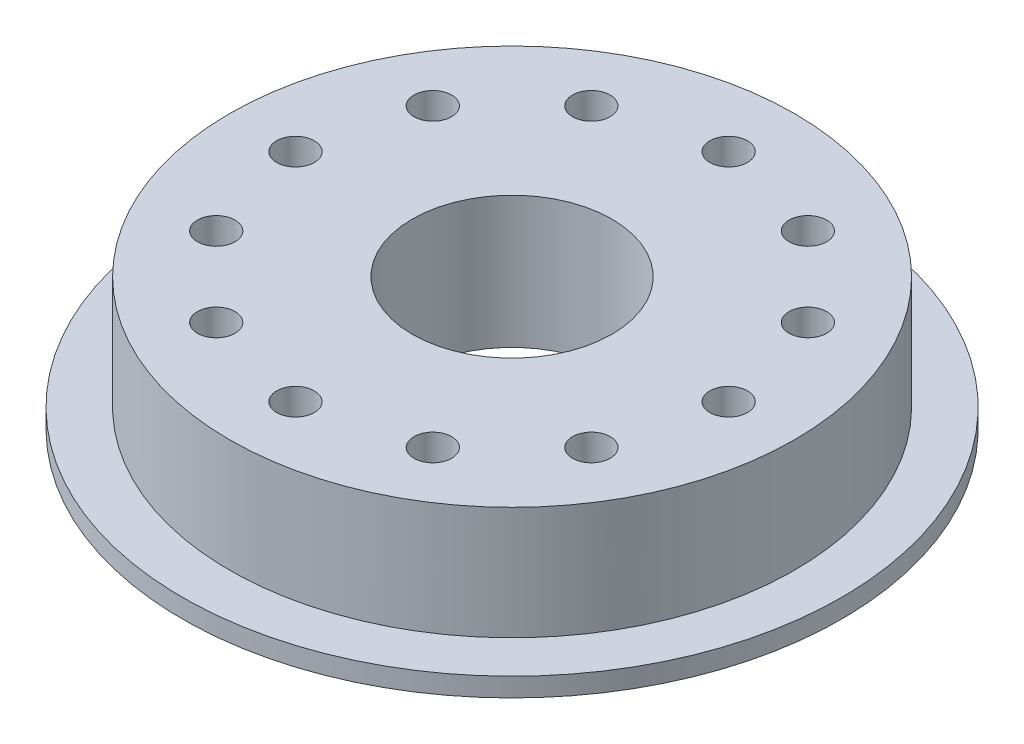
SolidWorks part; units mm, degrees
ref_plane "Front Plane" through (0, 0, 0) normal (0, 0, 1) x (1, 0, 0)
ref_plane "Top Plane" through (0, 0, 0) normal (0, 1, 0) x (1, 0, 0)
ref_plane "Right Plane" through (0, 0, 0) normal (1, 0, 0) x (0, 0, -1)
sketch "Sketch1" plane through (0, 0, 0) normal (0, 1, 0) x (1, 0, 0)
  circle A0 centre (0, 0) radius 30
  circle A1 centre (0, 0) radius 23 construction
  circle A8 centre (0, 0) radius 10.6
  point P18 (0, 0)
  dimension "D1" = 46
  dimension "D4" = 60
  dimension "D5" = 21.2
extrude "Boss-Extrude1" add sketch "Sketch1" along normal blind 14
sketch "Sketch2" plane through (0, 0, 0) normal (0, -1, 0) x (1, 0, 0)
  circle A0 centre (0, 0) radius 35
  dimension "D1" = 70
extrude "Boss-Extrude2" add sketch "Sketch2" against normal blind 2
sketch "Sketch3" plane through (0, 14, 0) normal (0, 1, 0) x (1, 0, 0)
  circle A0 centre (0, 0) radius 10.6
  circle A1 centre (0, 0) radius 23 construction
  circle A2 centre (0, 23) radius 2
  circle A3 centre (11.5, 19.9186) radius 2
  circle A4 centre (19.9186, 11.5) radius 2
  circle A5 centre (23, 0) radius 2
  circle A6 centre (19.9186, -11.5) radius 2
  circle A7 centre (11.5, -19.9186) radius 2
  circle A8 centre (0, -23) radius 2
  circle A9 centre (-11.5, -19.9186) radius 2
  circle A10 centre (-19.9186, -11.5) radius 2
  circle A11 centre (-23, 0) radius 2
  circle A12 centre (-19.9186, 11.5) radius 2
  circle A13 centre (-11.5, 19.9186) radius 2
  point P30 (0, 0)
  dimension "D1" = 46
  dimension "D2" = 4
extrude "Cut-Extrude1" cut sketch "Sketch3" against normal blind 64
